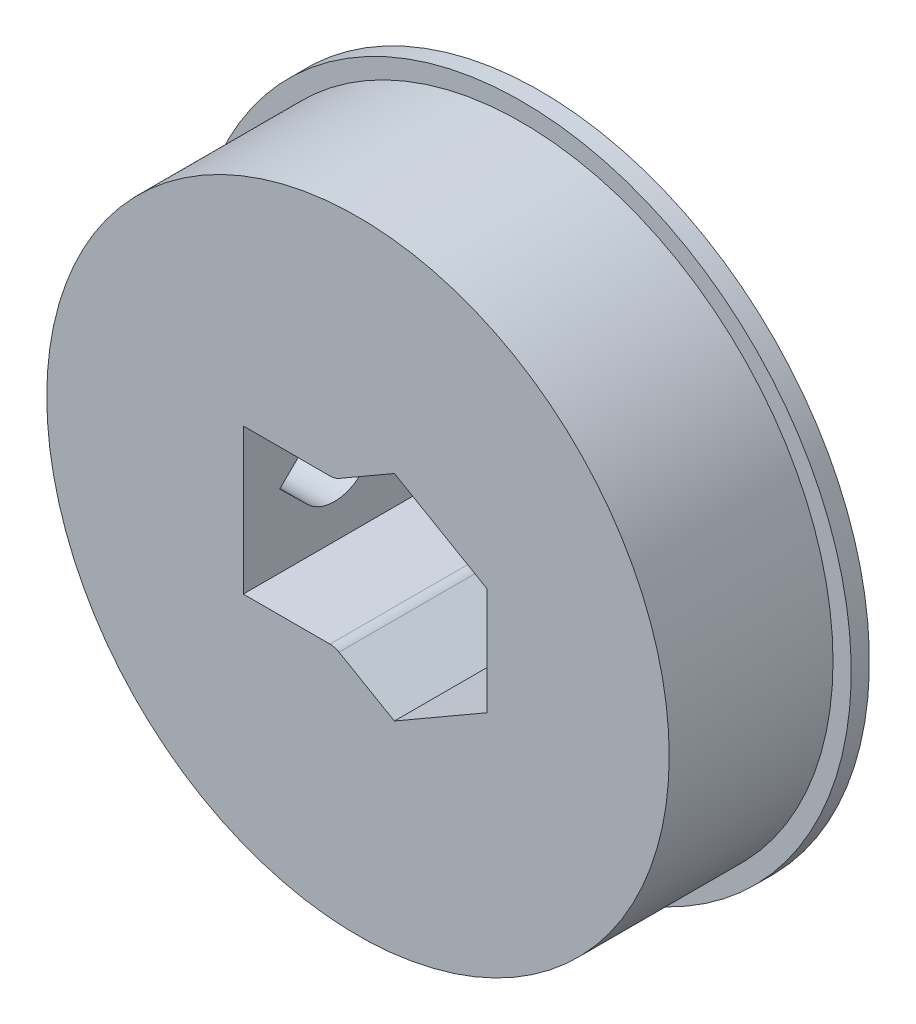
SolidWorks part; units mm, degrees
material "ABS"
ref_plane "Front Plane" through (0, 0, 0) normal (0, 0, 1) x (1, 0, 0)
ref_plane "Top Plane" through (0, 0, 0) normal (0, 1, 0) x (1, 0, 0)
ref_plane "Right Plane" through (0, 0, 0) normal (1, 0, 0) x (0, 0, -1)
sketch "Sketch1" plane through (0, 0, 0) normal (0, 0, 1) x (1, 0, 0)
  line L0 (0, 0) -> (-1, 0) construction
  line L1 (0, -2.9445) -> (2.55, -1.4722)
  line L2 (2.55, -1.4722) -> (2.55, 1.4722)
  line L3 (2.55, 1.4722) -> (0, 2.9445)
  line L4 (0, 2.9445) -> (-2.55, 1.4722)
  line L5 (-2.55, 1.4722) -> (-2.55, -1.4722)
  line L6 (-2.55, -1.4722) -> (0, -2.9445)
  circle A0 centre (0, 0) radius 2.55 construction
  circle A1 centre (-1, 0) radius 8.55
  dimension "D1" = 5.1
  dimension "D3" = 17.1
  dimension "D2" = 1
extrude "Boss-Extrude1" add sketch "Sketch1" along normal blind 5
sketch "Sketch2" plane through (-2.55, 0, 0) normal (1, 0, 0) x (0, 0, -1)
  line L0 (0, 0) -> (-5, 0) construction
  line L1 (-0.1906, 0) -> (-1.3453, 2) construction
  line L2 (-1.3453, 2) -> (-3.6547, 2) construction
  line L3 (-3.6547, 2) -> (-4.8094, 0) construction
  line L4 (-4.8094, 0) -> (-3.6547, -2) construction
  line L5 (-3.6547, -2) -> (-1.3453, -2) construction
  line L6 (-1.3453, -2) -> (-0.1906, 0) construction
  line L7 (0, 1.4722) -> (0, -1.4722) construction
  line L8 (-5, 1.4722) -> (-5, -1.4722) construction
  line L10 (0, -2) -> (-5, -2)
  line L11 (0, -2) -> (0, 2)
  line L12 (0, 2) -> (-5, 2)
  line L13 (-5, -2) -> (-5, 2)
  line L14 (0, -2) -> (-5, 2) construction
  line L15 (0, 2) -> (-5, -2) construction
  circle A0 centre (-2.5, 0) radius 2 construction
  dimension "D1" = 4
extrude "M2 Hexnut Cutout" cut sketch "Sketch2" against normal blind 1.6 and the other way blind 1.5
fillet "Fillet1" radius 0.5 2 edges at (-1.6359, -2, 2.5) (-1.6359, 2, 2.5)
sketch "Sketch3" plane through (-4.15, 0, 0) normal (1, 0, 0) x (0, 0, -1)
  line L0 (0, 0) -> (-5, 0) construction
  line L1 (0, -2) -> (0, 2) construction
  line L2 (-5, 2) -> (-5, -2) construction
  line L3 (-2.5, 0) -> (-1, 0) construction
  line L4 (-1, 0) -> (-1.765, 0.7498)
  line L5 (-1, 0) -> (-1.765, -0.7498)
  line L6 (-1, 0) -> (-1.765, -0.7498)
  line L7 (-1, 0) -> (-1.765, 0.7498)
  line L8 (-2.5, 0) -> (-2.5, 1.4001) construction
  line L9 (-4, 0) -> (-3.235, -0.7498)
  line L10 (-4, 0) -> (-3.235, 0.7498)
  arc A0 (-1.765, 0.7498) -> (-3.235, 0.7498) centre (-2.5, 0) ccw
  arc A1 (-1.765, 0.7498) -> (-3.235, 0.7498) centre (-2.5, 0) ccw
  arc A2 (-3.235, -0.7498) -> (-1.765, -0.7498) centre (-2.5, 0) ccw
  arc A3 (-3.235, -0.7498) -> (-1.765, -0.7498) centre (-2.5, 0) ccw
  dimension "D1" = 1.5
  dimension "M2 Thru" = 2.1
extrude "M2 Thru" cut sketch "Sketch3" against normal through all contours L9 A2 L5 L4 A0 L10 region at (-4.15, 0, 2.5)
sketch "Sketch4" plane through (0, 0, 0) normal (0, 0, -1) x (-1, 0, 0)
  circle A0 centre (1, 0) radius 8.55
  circle A1 centre (1, 0) radius 9.05
  circle A2 centre (1, 0) radius 8.55 construction
  dimension "D1" = 18.1
  dimension "D2" = 17.1
extrude "Boss-Extrude2" add sketch "Sketch4" against normal blind 0.5
equation "\"D1@Sketch4\"=\"D2@Sketch4\"+1"
